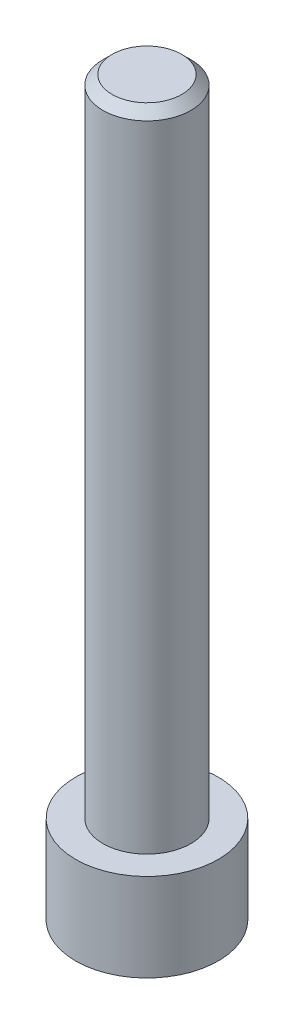
SolidWorks part; units mm, degrees
ref_plane "Front Plane" through (0, 0, 0) normal (0, 0, 1) x (1, 0, 0)
ref_plane "Top Plane" through (0, 0, 0) normal (0, 1, 0) x (1, 0, 0)
ref_plane "Right Plane" through (0, 0, 0) normal (1, 0, 0) x (0, 0, -1)
sketch "Sketch1" plane through (0, 0, 0) normal (0, 1, 0) x (1, 0, 0)
  line L1 (4.4745, 0) -> (2.2372, 3.875) construction
  line L2 (2.2372, 3.875) -> (-2.2372, 3.875) construction
  line L3 (-2.2372, 3.875) -> (-4.4745, 0) construction
  line L4 (-4.4745, 0) -> (-2.2372, -3.875) construction
  line L5 (-2.2372, -3.875) -> (2.2372, -3.875) construction
  line L6 (2.2372, -3.875) -> (4.4745, 0) construction
  circle A0 centre (0, 0) radius 3.875
  dimension "D1" = 7.75
extrude "Boss-Extrude1" add sketch "Sketch1" along normal blind 39.78
sketch "Sketch2" plane through (0, 39.78, 0) normal (0, 1, 0) x (1, 0, 0)
  circle A0 centre (0, 0) radius 2.39
  dimension "D1" = 4.78
extrude "Cut-Extrude1" cut sketch "Sketch2" against normal blind 35 flip side to cut
ref_axis "Axis1" through (0, 4.78, 0) along (0, 1, 0)
chamfer "Chamfer1" distance 0.5 angle 45 1 edges at (0, 39.78, 2.39)
sketch "Sketch5" plane through (0, 39.78, 0) normal (0, 1, 0) x (1, 0, 0)
  circle A0 centre (0, 0) radius 2.39
  dimension "D1" = 4.78
curve "Helix/Spiral1" pitch 0.7 height 25 turns 35.7143
ref_plane "Plane1" through (0, 39.78, 2.39) normal (-0.9989, -0.0466, 0) x (0, 0, 1)
sketch "Sketch8" plane through (0, 0, 0) normal (0, -1, 0) x (1, 0, 0)
  line L1 (2.6443, 0) -> (1.3221, 2.29)
  line L2 (1.3221, 2.29) -> (-1.3221, 2.29)
  line L3 (-1.3221, 2.29) -> (-2.6443, 0)
  line L4 (-2.6443, 0) -> (-1.3221, -2.29)
  line L5 (-1.3221, -2.29) -> (1.3221, -2.29)
  line L6 (1.3221, -2.29) -> (2.6443, 0)
  circle A0 centre (0, 0) radius 2.29 construction
  dimension "D1" = 4.58
extrude "Cut-Extrude2" cut sketch "Sketch8" against normal blind 3.36
